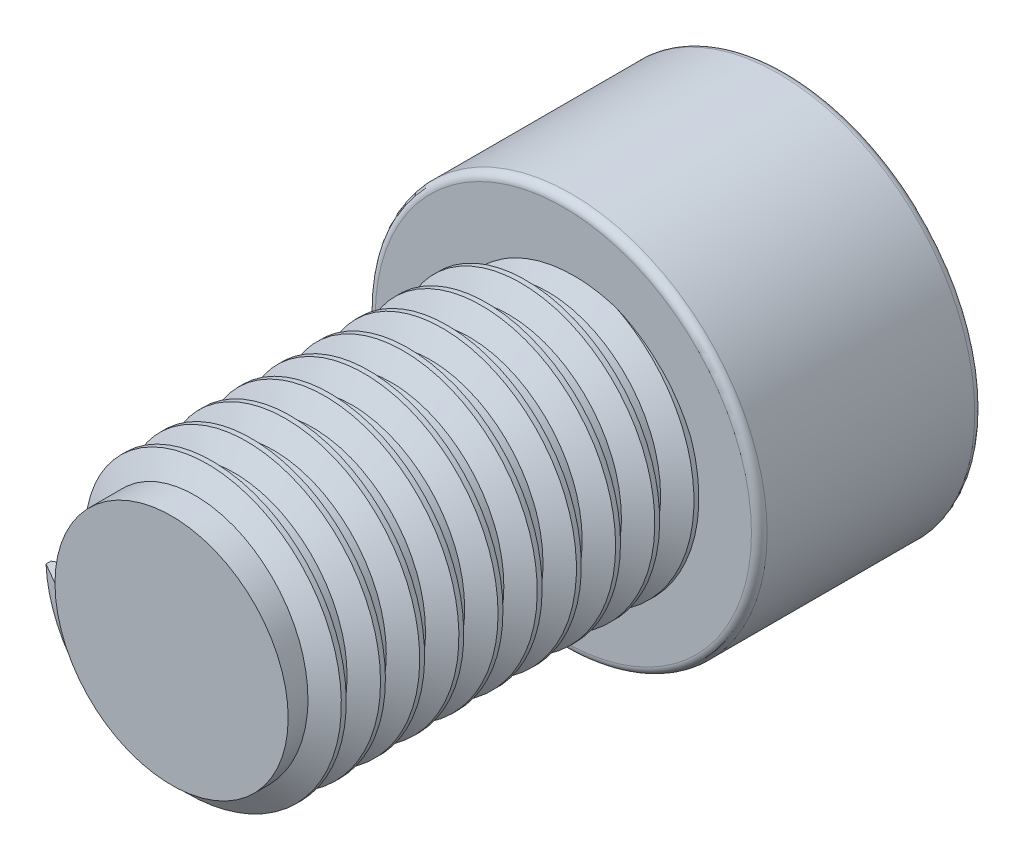
SolidWorks part; units mm, degrees
ref_plane "Front Plane" through (0, 0, 0) normal (0, 0, 1) x (1, 0, 0)
ref_plane "Top Plane" through (0, 0, 0) normal (0, 1, 0) x (1, 0, 0)
ref_plane "Right Plane" through (0, 0, 0) normal (1, 0, 0) x (0, 0, -1)
sketch "Sketch1" plane through (0, 0, 0) normal (0, 0, 1) x (1, 0, 0)
  line L0 (0, 0) -> (0, 4.4885) construction
  line L7 (0, 0) -> (4.3151, 0) construction
  line L9 (0, 2.8868) -> (-2.5, 1.4434)
  line L10 (-2.5, 1.4434) -> (-2.5, -1.4434)
  line L11 (-2.5, -1.4434) -> (0, -2.8868)
  line L12 (0, -2.8868) -> (2.5, -1.4434)
  line L13 (2.5, -1.4434) -> (2.5, 1.4434)
  line L14 (2.5, 1.4434) -> (0, 2.8868)
  circle A0 centre (0, 0) radius 5
  circle A1 centre (0, 0) radius 2.5 construction
  dimension "D1" = 10
  dimension "D2" = 5
extrude "Boss-Extrude1" add sketch "Sketch1" along normal blind 5.7
sketch "Sketch2" plane through (0, 0, 0) normal (0, 0, -1) x (-1, 0, 0)
  circle A0 centre (0, 0) radius 2.9125
extrude "Cut-Extrude1" cut sketch "Sketch2" against normal blind 0.5
sketch "Sketch3" plane through (0, 0, 5.7) normal (0, 0, 1) x (1, 0, 0)
  circle A0 centre (0, 0) radius 2.9761
extrude "Boss-Extrude2" add sketch "Sketch3" along normal blind 10
fillet "Fillet1" radius 0.2 2 edges at (5, 0, 5.7) (5, 0, 0)
thread "Thread1" start angle 0, offset 0, length 0, pitch 1, diameter 5.9521
ref_plane "Plane1" through (-2.9761, 0, 15.7) normal (0, -1, 0) x (-1, 0, 0)
sketch "Thread Profile1" plane through (-2.9761, 0, 15.7) normal (0, -1, 0) x (-1, 0, 0)
  line L0 (0, 0) -> (0, 1) construction
  line L1 (0, 0) -> (0.5413, 0.3125)
  line L2 (0.5413, 0.3125) -> (0.5413, 0.4375)
  line L3 (0.5413, 0.4375) -> (0, 0.75)
  line L4 (0.5413, 0.375) -> (0, 0.375) construction
  line L11 (0, 0) -> (0, 0.75)
  point P2 (0, 0)
  dimension "Pitch" = 1
  dimension "Profile_Angle" = 60
  dimension "Profile_Land" = 0.125
  dimension "Profile_Height" = 0.5413
